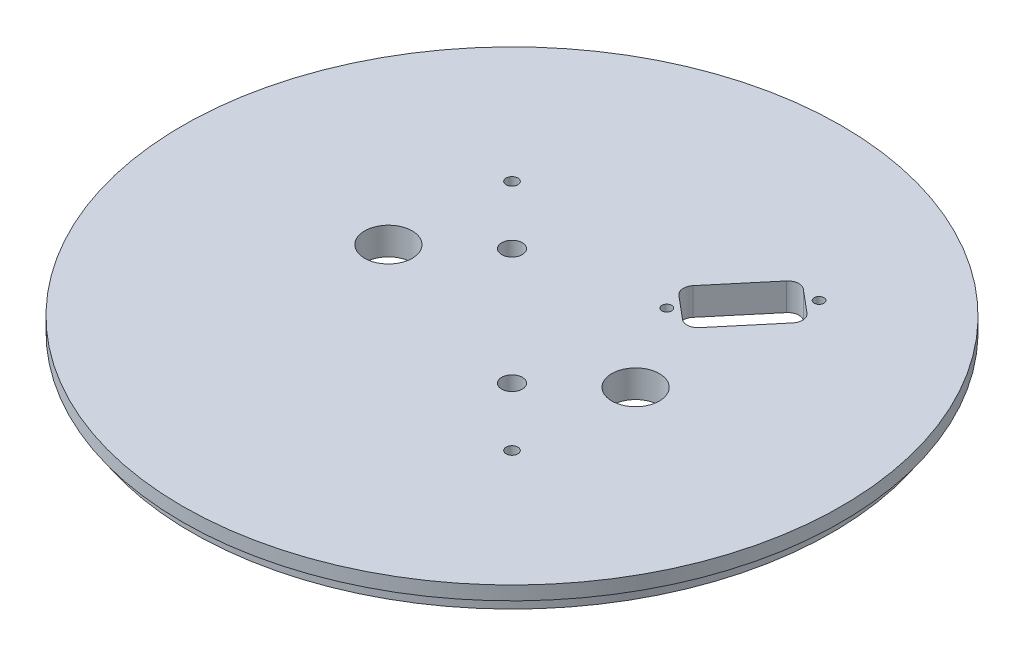
SolidWorks part; units mm, degrees
material "6061-T6 (SS)"
ref_plane "Front Plane" through (0, 0, 0) normal (0, 0, 1) x (1, 0, 0)
ref_plane "Top Plane" through (0, 0, 0) normal (0, 1, 0) x (1, 0, 0)
ref_plane "Right Plane" through (0, 0, 0) normal (1, 0, 0) x (0, 0, -1)
sketch "Sketch1" plane through (0, 0, 0) normal (0, 1, 0) x (1, 0, 0)
  line L0 (0, -76.2) -> (0, 76.2) construction
  line L1 (-76.2, 0) -> (76.2, 0) construction
  line L2 (-26.9408, 26.9408) -> (0, 0) construction
  line L3 (0, 56.7387) -> (0, 29.6936) construction
  line L4 (3.6407, 56.7387) -> (3.6407, 29.6936) construction
  line L5 (-3.6407, 56.7387) -> (-3.6407, 29.6936) construction
  line L6 (0, -56.7387) -> (0, -29.6936) construction
  line L7 (3.6407, -56.7387) -> (3.6407, -29.6936) construction
  line L8 (-3.6407, -56.7387) -> (-3.6407, -29.6936) construction
  line L9 (-53.8815, -53.8815) -> (54.3236, 54.3236) construction
  circle A0 centre (0, 0) radius 76.2
  circle A1 centre (0, 0) radius 3.175 construction
  circle A2 centre (28.575, 0) radius 5.5
  circle A3 centre (-28.575, 0) radius 5.5
  circle A4 centre (-26.9408, 26.9408) radius 1.3589
  arc A6 (3.6407, 56.7387) -> (-3.6407, 56.7387) centre (0, 56.7387) ccw construction
  arc A7 (-3.6407, 29.6936) -> (3.6407, 29.6936) centre (0, 29.6936) ccw construction
  arc A8 (3.6407, -56.7387) -> (-3.6407, -56.7387) centre (0, -56.7387) cw construction
  arc A9 (-3.6407, -29.6936) -> (3.6407, -29.6936) centre (0, -29.6936) cw construction
  circle A10 centre (26.9408, -26.9408) radius 1.3589
  circle A11 centre (-13.4704, 13.4704) radius 2.3813
  circle A12 centre (13.4704, -13.4704) radius 2.3813
  point P16 (0, 43.2162)
  point P19 (0, 0)
  point P26 (0, -43.2162)
  dimension "D1" = 152.4
  dimension "D2" = 6.35
  dimension "D3" = 11
  dimension "D5" = 2.7178
  dimension "D8" = 4.7625
  dimension "D6" = 38.1
  dimension "D7" = 45
  dimension "D4" = 45
  dimension "D9" = 28.575
extrude "Boss-Extrude1" add sketch "Sketch1" along normal blind 6.35
sketch "Sketch2" plane through (0, 0, 0) normal (0, -1, 0) x (1, 0, 0)
  circle A0 centre (0, 0) radius 76.2
  circle A1 centre (0, 0) radius 74.041
  dimension "D1" = 152.4
  dimension "D2" = 148.082
extrude "Cut-Extrude1" cut sketch "Sketch2" against normal blind 3.175
sketch "Sketch3" plane through (0, 6.35, 0) normal (0, 1, 0) x (1, 0, 0)
  line L0 (0, 76.2) -> (0, -76.2) construction
  line L1 (-76.2, 0) -> (76.2, 0) construction
  line L2 (0, 34.798) -> (0, 13.97) construction
  line L3 (3.2385, 34.798) -> (3.2385, 13.97)
  line L4 (-3.2385, 34.798) -> (-3.2385, 13.97)
  line L5 (0, -34.798) -> (0, -13.97) construction
  line L6 (3.2385, -34.798) -> (3.2385, -13.97)
  line L7 (-3.2385, -34.798) -> (-3.2385, -13.97)
  circle A0 centre (0, 0) radius 76.2 construction
  arc A1 (3.2385, 34.798) -> (-3.2385, 34.798) centre (0, 34.798) ccw
  arc A2 (-3.2385, 13.97) -> (3.2385, 13.97) centre (0, 13.97) ccw
  arc A3 (3.2385, -34.798) -> (-3.2385, -34.798) centre (0, -34.798) cw
  arc A4 (-3.2385, -13.97) -> (3.2385, -13.97) centre (0, -13.97) cw
  point P7 (0, 13.97)
  point P8 (0, 34.798)
  point P12 (0, 24.384)
  point P20 (0, -24.384)
  point P25 (0, -34.798)
  point P26 (0, -13.97)
  dimension "D1" = 13.97
  dimension "D2" = 20.828
  dimension "D3" = 6.477
extrude "Cut-Extrude2" cut sketch "Sketch3" against normal blind 3.556 from offset 5.969 offset against normal yes
hole_wizard "Tap Drill for #4-40 Tap1" positions "Sketch5" profile "Sketch6" hole size "#4-40" standard "ANSI Inch" end condition through all
sketch "Sketch5" plane through (0, 6.35, 0) normal (0, 1, 0) x (1, 0, 0)
  line L0 (0, 0) -> (53.6567, 63.9455) construction
  line L2 (0, 0) -> (28.575, 0) construction
  point P0 (16.3268, 19.4575)
  point P2 (32.3965, 38.6086)
  dimension "D1" = 50
  dimension "D2" = 25
  dimension "D3" = 25.4
sketch "Sketch6" plane through (16.3268, 6.35, -19.4575) normal (1, 0, 0) x (0, 0, 1)
  line L0 (0, 0) -> (0, 6.35)
  line L1 (0, 6.35) -> (1.1303, 6.35)
  line L2 (1.1303, 6.35) -> (1.1303, 0)
  line L5 (1.1303, 0) -> (0, 0)
  line L11 (0, -6.35) -> (0, 107.95) construction
  dimension "Thru Hole Dia." = 2.2606
  dimension "Thru Hole Depth" = 6.35
sketch "Sketch4" plane through (0, 6.35, 0) normal (0, 1, 0) x (1, 0, 0)
  line L0 (15.1695, 23.4128) -> (20.423, 19.0046)
  line L1 (14.8564, 26.9913) -> (24.7219, 38.7485)
  line L2 (24.0014, 19.3177) -> (33.8669, 31.0749)
  line L3 (28.3003, 39.0616) -> (33.5538, 34.6533)
  line L4 (0, 0) -> (32.3965, 38.6086) construction
  circle A1 centre (16.3268, 19.4575) radius 1.1303 construction
  arc A2 (24.7219, 38.7485) -> (28.3003, 39.0616) centre (26.6676, 37.1158) cw
  arc A3 (33.8669, 31.0749) -> (33.5538, 34.6533) centre (31.9212, 32.7076) ccw
  arc A4 (20.423, 19.0046) -> (24.0014, 19.3177) centre (22.0557, 20.9503) ccw
  arc A5 (14.8564, 26.9913) -> (15.1695, 23.4128) centre (16.8021, 25.3586) ccw
  point P11 (17.7962, 21.2087)
  dimension "D4" = 2.54
  dimension "D1" = 2.286
  dimension "D2" = 2.286
  dimension "D3" = 11.938
extrude "Cut-Extrude3" cut sketch "Sketch4" against normal through all
equation "\"leadDist\"=1.5"
equation "\"Lead_Screw_Dist\" = 2.25in"
equation "\"D9@Sketch1\"=\"Lead_Screw_Dist\"/2"
equation "\"Lead_Screw_Diam\" = 11mm"
equation "\"D3@Sketch1\"=\"Lead_Screw_Diam\""
equation "\"Bodytube_OD\" = 6.17in"
equation "\"Bodytube_ID\" = 5.998in"
equation "\"Motor_OD\" = 4in"
equation "\"Fwd_Tube_Length\" = 40in"
equation "\"Mid_Tube_Length\" = 1in"
equation "\"Aft_Section_Length\"= 39in"
equation "\"AB_Coupler_OD_Length\"= 1in"
equation "\"AB_Coupling_Section_Length\"= 0.375in"
equation "\"AB_Coupler_Length\"= \"AB_Coupler_OD_Length\" + \"AB_Coupling_Section_Length\" * 2"
equation "\"Cutout_Angle\" = 80"
equation "\"AB_Paddle_Height\" = 0.375in"
equation "\"AB_Coupler_Num_Screws\"= 6"
equation "\"Num_Cutouts\" = 3"
equation "\"AB_Coupler_OD\"= 6.17in"
equation "\"AB_Coupler_ID\"= 5.75in"
equation "\"AB_Coupler_Surface_Diameter\"= 5.998in"
equation "\"AB_Coupling_Screw_Diameter\"= 0.1065in"
equation "\"AB_Central_Bushing_Length\" = .75in"
equation "\"Lead_Screw_Length\" = (\"Mid_Coupler_Length\" + 2*0.375in + 2*0.5in)"
equation "\"Paddle_Pin_Offset\" = .25in"
equation "\"Paddle_Pin_Radius\" = 2.25in"
equation "\"SS_Paddle_Pin_Radius\" = 2.25*0.66in"
equation "\"Paddle_Gear_OD\" = 3.2in"
equation "\"Drive_Gear_OD\" = 1.7in"
equation "\"Fwd_BKHD_From_Top\" = 18in"
equation "\"Fin_Thickness\"= .118in"
equation "\"Guiderail_Cutout_Diameter\"= 1.5in"
equation "\"DB9_Hole_Dist\" = 25mm"
equation "\"Airbrakes_Wire_Hole_Dia\" = .25in"
equation "\"Airbrakes_Wire_Hole_Dist\" = 1.1in"
equation "\"Servo_Gear_Offset\" = 0.5in"
equation "\"Mid_Coupler_Length\" = 13in"
equation "\"D2@Sketch5\"=\"DB9_Hole_Dist\""
equation "\"DB9_Relief_Width\" = 0.47in"
equation "\"DB9_Relief_Hole_Offset\" = 0.09in"
equation "\"D1@Sketch4\"=\"DB9_Relief_Hole_Offset\""
equation "\"D2@Sketch4\"=\"DB9_Relief_Hole_Offset\""
equation "\"D3@Sketch4\"=\"DB9_Relief_Width\""
